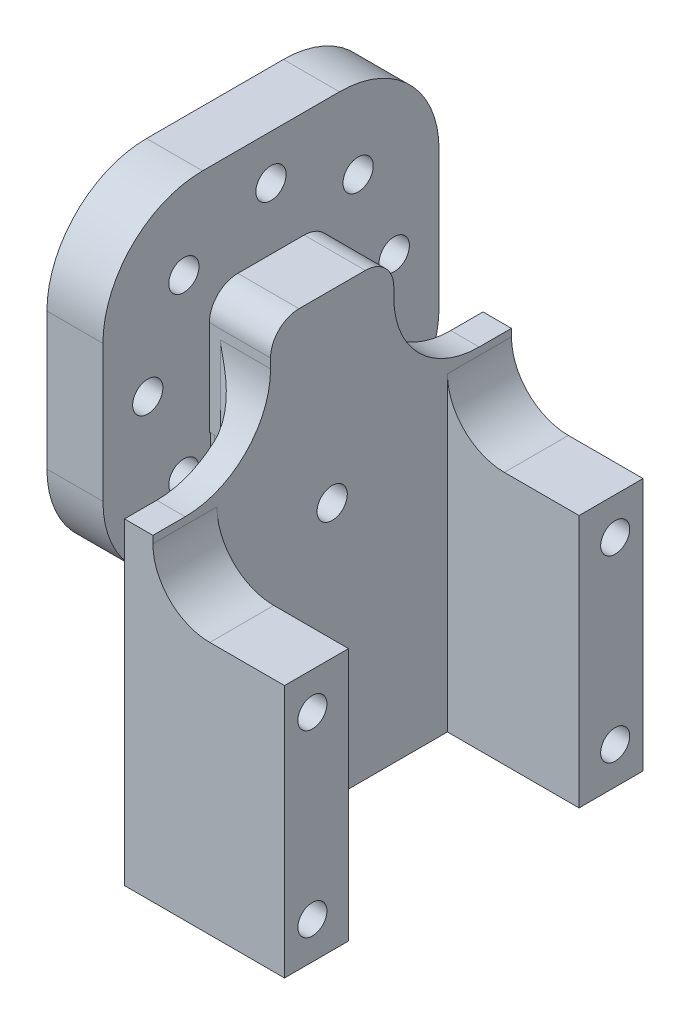
SolidWorks part; units mm, degrees
material "ABS PC"
ref_plane "Front Plane" through (0, 0, 0) normal (0, 0, 1) x (1, 0, 0)
ref_plane "Top Plane" through (0, 0, 0) normal (0, 1, 0) x (1, 0, 0)
ref_plane "Right Plane" through (0, 0, 0) normal (1, 0, 0) x (0, 0, -1)
sketch "Sketch1" plane through (0, 0, 0) normal (0, 0, 1) x (1, 0, 0)
  line L0 (-3.796, -4.492) -> (-3.796, 57.658)
  line L1 (-3.796, 57.658) -> (44.704, 57.658)
  line L2 (44.704, 57.658) -> (44.704, 20.908)
  line L3 (-3.796, -4.492) -> (1.204, -4.492)
  line L4 (1.204, -4.492) -> (1.204, 52.658)
  line L5 (1.204, 52.658) -> (39.704, 52.658)
  line L6 (39.704, 52.658) -> (39.704, 20.908)
  line L7 (39.704, 20.908) -> (44.704, 20.908)
  dimension "D1" = 5
  dimension "D2" = 31.75
  dimension "D3" = 5
  dimension "D4" = 48.5
  dimension "D5" = 57.15
  dimension "D6" = 5
extrude "Boss-Extrude1" add sketch "Sketch1" along normal blind 45
sketch "Sketch4" plane through (44.704, 0, 0) normal (1, 0, 0) x (0, 0, -1)
  line L1 (0, 20.908) -> (0, 57.658) construction
  line L3 (-45, 20.908) -> (-45, 57.658) construction
  line L4 (-45, 20.908) -> (0, 20.908) construction
  circle A0 centre (-22.6336, 47.4432) radius 1.35
  circle A1 centre (-22.6336, 25.448) radius 1.35
  circle A2 centre (-11.6341, 36.4435) radius 1.35
  circle A3 centre (-33.6321, 36.4435) radius 1.35
  dimension "D3" = 22.6336
  dimension "D4" = 15.5355
  dimension "D6" = 2.7
  dimension "D7" = 2.7
  dimension "D8" = 2.7
  dimension "D9" = 2.7
  dimension "D11" = 11.6341
  dimension "D12" = 4.54
  dimension "D13" = 26.5352
  dimension "D5" = 15.5355
  dimension "D2" = 22.6336
  dimension "D10" = 11.3679
extrude "Cut-Extrude3" cut sketch "Sketch4" against normal through all
sketch "Sketch16" plane through (0, 0, 45) normal (0, 0, 1) x (1, 0, 0)
  line L1 (39.704, -16.37) -> (-14.8974, -16.37)
  line L2 (39.704, -16.37) -> (39.704, 64.193)
  line L3 (39.704, 64.193) -> (-14.8974, 64.193)
  line L4 (-14.8974, -16.37) -> (-14.8974, 64.193)
extrude "Cut-Extrude6" cut sketch "Sketch16" against normal through all
sketch "Sketch17" plane through (44.704, 0, 0) normal (1, 0, 0) x (0, 0, -1)
  line L0 (-33.6321, 36.4435) -> (-11.6341, 36.4435)
  line L1 (-22.6336, 47.4432) -> (-22.6336, 25.448)
  line L3 (-37.6331, 51.4435) -> (-7.6331, 51.4435)
  line L4 (-37.6331, 51.4435) -> (-37.6331, 21.4435)
  line L5 (-37.6331, 21.4435) -> (-7.6331, 21.4435)
  line L6 (-7.6331, 51.4435) -> (-7.6331, 21.4435)
  line L7 (-37.6331, 51.4435) -> (-7.6331, 21.4435) construction
  line L8 (-37.6331, 21.4435) -> (-7.6331, 51.4435) construction
  point P8 (-22.6331, 36.4435)
  line M1 (0, 57.658) -> (-45, 57.658)
  line M2 (-45, 57.658) -> (-45, 20.908)
  line M3 (-45, 20.908) -> (0, 20.908)
  line M4 (0, 20.908) -> (0, 57.658)
  dimension "D1" = 30
extrude "Cut-Extrude7" cut sketch "Sketch17" against normal through all contours L3 L6 L5 L4 M4 M1 M2 M3 region at (44.704, 39.283, 0.581)
sketch "Sketch18" plane through (44.704, 0, 0) normal (1, 0, 0) x (0, 0, -1)
  line L0 (-22.6336, 47.4432) -> (-22.6336, 25.448)
  line L1 (-33.6321, 36.4435) -> (-11.6341, 36.4435)
  line L2 (-14.8572, 44.222) -> (-22.6336, 36.4456)
  line L3 (-30.4104, 28.6688) -> (-22.6336, 36.4456)
  line L4 (-14.8568, 28.6688) -> (-22.6336, 36.4456)
  circle A0 centre (-14.8572, 44.222) radius 1.35
  circle A2 centre (-30.4104, 28.6688) radius 1.35
  circle A3 centre (-14.8568, 28.6688) radius 1.35
  circle A4 centre (-30.4104, 44.222) radius 1.35
  dimension "D3" = 2.7
  dimension "D6" = 2.7
  dimension "D9" = 2.7
  dimension "D12" = 2.7
  dimension "D1" = 21.998
  dimension "D2" = 21.9952
  dimension "D4" = 45
  dimension "D5" = 10.9975
  dimension "D7" = 10.998
  dimension "D8" = 180
  dimension "D10" = 10.998
  dimension "D11" = 45
extrude "Cut-Extrude8" cut sketch "Sketch18" against normal through all contours A4 | A0 | A3 | A2 region at (44.704, 45.434, 15.3592) region at (44.704, 29.8808, 14.3548) region at (44.704, 29.1708, 29.1984) region at (44.704, 44.222, 30.4104)
fillet "Fillet1" radius 8.89 4 edges at (42.204, 21.4435, 37.6331) (42.204, 21.4435, 7.6331) (42.204, 51.4435, 7.6331) (42.204, 51.4435, 37.6331)
sketch "Sketch19" plane through (44.704, 0, 0) normal (1, 0, 0) x (0, 0, -1)
  line L1 (-28.1336, 41.9435) -> (-17.1336, 41.9435)
  line L2 (-28.1336, 41.9435) -> (-28.1336, 30.9435)
  line L3 (-28.1336, 30.9435) -> (-17.1336, 30.9435)
  line L4 (-17.1336, 41.9435) -> (-17.1336, 30.9435)
  line L5 (-28.1336, 41.9435) -> (-17.1336, 30.9435) construction
  line L6 (-28.1336, 30.9435) -> (-17.1336, 41.9435) construction
  point P0 (-22.6336, 36.4435)
  dimension "D1" = 11
extrude "Boss-Extrude2" add sketch "Sketch19" along normal blind 2.921
sketch "Sketch20" plane through (47.625, 0, 0) normal (1, 0, 0) x (0, 0, -1)
  line L1 (-25.1336, 38.9435) -> (-20.1336, 38.9435)
  line L2 (-25.1336, 38.9435) -> (-25.1336, 33.9435)
  line L3 (-25.1336, 33.9435) -> (-20.1336, 33.9435)
  line L4 (-20.1336, 38.9435) -> (-20.1336, 33.9435)
  line L5 (-25.1336, 38.9435) -> (-20.1336, 33.9435) construction
  line L6 (-25.1336, 33.9435) -> (-20.1336, 38.9435) construction
  point P0 (-22.6336, 36.4435)
  dimension "D1" = 5
extrude "Cut-Extrude9" cut sketch "Sketch20" against normal blind 25
sketch "Sketch25" plane through (39.704, 0, 0) normal (-1, 0, 0) x (0, 0, 1)
  line L0 (7.6331, 36.4435) -> (37.6331, 36.4435) construction
  line L1 (7.6331, 42.5535) -> (7.6331, 30.3335) construction
  line L2 (37.6331, 42.5535) -> (37.6331, 30.3335) construction
  line L3 (22.6331, 51.4435) -> (22.6331, 21.4435) construction
  line L4 (28.7431, 51.4435) -> (16.5231, 51.4435) construction
  line L5 (28.7431, 21.4435) -> (16.5231, 21.4435) construction
  circle A0 centre (22.6331, 36.4435) radius 1.5
  dimension "D1" = 3
sketch "Sketch26" plane through (47.625, 0, 0) normal (1, 0, 0) x (0, 0, -1)
  line L0 (-17.1336, 41.9435) -> (-28.1336, 41.9435) construction
  line L1 (-38.6356, 45.8048) -> (-6.6316, 45.8048)
  line L2 (-38.6356, 45.8048) -> (-38.6356, 2.5994)
  line L3 (-38.6356, 2.5994) -> (-6.6316, 2.5994)
  line L4 (-6.6316, 45.8048) -> (-6.6316, 2.5994)
  point P4 (-22.6336, 41.9435)
  dimension "D1" = 43.2054
  dimension "D2" = 32.004
  dimension "D3" = 16.002
extrude "Boss-Extrude3" add sketch "Sketch26" along normal blind 2.54
sketch "Sketch27" plane through (50.165, 0, 0) normal (1, 0, 0) x (0, 0, -1)
  line L0 (-38.6356, 45.8048) -> (-38.6356, 2.5994) construction
  line L1 (-38.6356, 25.2054) -> (-6.6316, 25.2054)
  line L2 (-38.6356, 25.2054) -> (-38.6356, 2.5994)
  line L3 (-38.6356, 2.5994) -> (-6.6316, 2.5994)
  line L4 (-6.6316, 25.2054) -> (-6.6316, 2.5994)
  line L5 (-6.6316, 2.5994) -> (-6.6316, 45.8048) construction
  line L6 (-38.6356, 2.5994) -> (-6.6316, 2.5994) construction
  dimension "D1" = 22.606
  dimension "D2" = 0
extrude "Boss-Extrude4" add sketch "Sketch27" along normal blind 11.7475
sketch "Sketch28" plane through (61.9125, 0, 0) normal (1, 0, 0) x (0, 0, -1)
  line L0 (-6.6316, 2.5994) -> (-6.6316, 25.2054) construction
  line L1 (-6.6316, 25.2054) -> (-38.6356, 25.2054) construction
  line L2 (-38.6356, 2.5994) -> (-6.6316, 2.5994) construction
  line L3 (-22.6336, 25.2054) -> (-22.6336, 2.5994) construction
  circle A0 centre (-9.1208, 21.9034) radius 1.2954
  circle A1 centre (-9.1208, 5.9014) radius 1.2954
  circle A2 centre (-36.1464, 5.9014) radius 1.2954
  circle A3 centre (-36.1464, 21.9034) radius 1.2954
  dimension "D1" = 2.5908
  dimension "D4" = 2.5908
  dimension "D2" = 2.4892
  dimension "D3" = 3.302
  dimension "D5" = 2.4892
  dimension "D6" = 3.302
extrude "Cut-Extrude11" cut sketch "Sketch28" against normal blind 19.05
sketch "Sketch30" plane through (47.625, 0, 0) normal (-1, 0, 0) x (0, 0, 1)
  line L0 (9.1208, 21.9034) -> (9.1208, 5.9014) construction
  line L1 (36.1464, 21.9034) -> (36.1464, 5.9014) construction
  circle A0 centre (9.1208, 13.9024) radius 1.2954
  circle A1 centre (36.1464, 13.9024) radius 1.2954
  dimension "D1" = 2.5908
  dimension "D2" = 2.5908
extrude "Cut-Extrude13" [suppressed] cut sketch "Sketch30" against normal blind 19.05
sketch "Sketch31" plane through (50.165, 0, 0) normal (1, 0, 0) x (0, 0, -1)
  line L0 (-38.6356, 45.8048) -> (-38.6356, 30.9435)
  line L1 (-38.6356, 45.8048) -> (-38.6356, 25.2054) construction
  line L2 (-38.6356, 30.9435) -> (-28.1336, 30.9435)
  line L3 (-28.1336, 30.9435) -> (-28.1336, 41.9435)
  line L4 (-28.1336, 41.9435) -> (-17.1336, 41.9435)
  line L5 (-17.1336, 41.9435) -> (-17.1336, 30.9435)
  line L6 (-17.1336, 30.9435) -> (-6.6316, 30.9435)
  line L7 (-6.6316, 25.2054) -> (-6.6316, 45.8048) construction
  line L8 (-6.6316, 30.9435) -> (-6.6316, 45.8048)
  line L9 (-6.6316, 45.8048) -> (-38.6356, 45.8048)
extrude "Cut-Extrude14" cut sketch "Sketch31" against normal blind 3.81
sketch "Sketch32" plane through (0, 0, 17.1336) normal (0, 0, -1) x (-1, 0, 0)
  line L1 (-47.625, 30.9435) -> (-44.704, 30.9435)
  line L2 (-47.625, 30.9435) -> (-47.625, 21.4435)
  line L3 (-47.625, 21.4435) -> (-44.704, 21.4435)
  line L4 (-44.704, 30.9435) -> (-44.704, 21.4435)
extrude "Boss-Extrude5" add sketch "Sketch32" against normal blind 10.922
sketch "Sketch33" plane through (0, 25.2054, 0) normal (0, 1, 0) x (1, 0, 0)
  line L0 (50.165, -12.3466) -> (61.9125, -12.3466)
  line L1 (50.165, -12.3466) -> (50.165, -32.9206)
  line L2 (61.9125, -12.3466) -> (61.9125, -32.9206)
  line L3 (50.165, -32.9206) -> (61.9125, -32.9206)
  line L4 (50.165, -12.3466) -> (61.9125, -32.9206) construction
  line L5 (61.9125, -12.3466) -> (50.165, -32.9206) construction
  point P1 (56.0388, -22.6336)
  dimension "D1" = 20.574
extrude "Cut-Extrude15" cut sketch "Sketch33" against normal through all
fillet "Fillet2" radius 5.08 1 edges
fillet "Fillet3" radius 5.08 1 edges
fillet "Fillet4" radius 7.62 1 edges at (47.625, 21.4435, 22.5946)
fillet "Fillet5" radius 7.62 1 edges at (48.895, 30.9435, 17.1336)
fillet "Fillet6" radius 7.62 1 edges at (48.895, 30.9435, 28.1336)
fillet "Fillet7" radius 2.54 1 edges at (47.4345, 41.9435, 28.1336)
fillet "Fillet8" radius 2.54 1 edges at (47.4345, 41.9435, 17.1336)
fillet "Fillet9" radius 2.54 1 edges at (47.625, 22.3835, 28.0556)
fillet "Fillet10" radius 2.54 1 edges at (47.625, 26.1935, 17.1336)
sketch "Sketch34" plane through (39.704, 0, 0) normal (-1, 0, 0) x (0, 0, 1)
  circle A0 centre (22.6336, 25.448) radius 1.35
extrude "Cut-Extrude16" cut sketch "Sketch34" against normal blind 11.43
